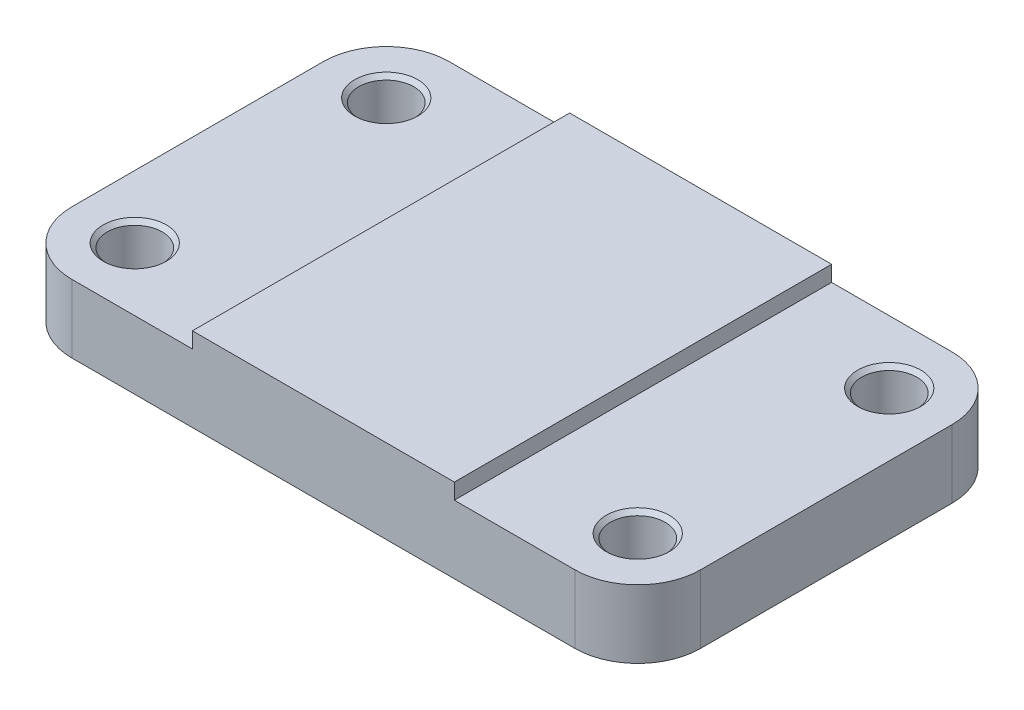
SolidWorks part; units mm, degrees
material "Ductile Iron"
ref_plane "Front Plane" through (0, 0, 0) normal (0, 0, 1) x (1, 0, 0)
ref_plane "Top Plane" through (0, 0, 0) normal (0, 1, 0) x (1, 0, 0)
ref_plane "Right Plane" through (0, 0, 0) normal (1, 0, 0) x (0, 0, -1)
sketch "Sketch1" plane through (0, 0, 0) normal (0, 0, 1) x (1, 0, 0)
  line L0 (0, -50.4344) -> (0, 50.4344) construction
  line L1 (-60, -6.5) -> (60, -6.5)
  line L2 (-60, -6.5) -> (-60, 6.5)
  line L3 (-60, 6.5) -> (60, 6.5)
  line L4 (60, -6.5) -> (60, 6.5)
  line L5 (-60, -6.5) -> (60, 6.5) construction
  line L6 (-60, 6.5) -> (60, -6.5) construction
  line L7 (-25, 6.5) -> (25, 6.5)
  line L8 (-25, 6.5) -> (-25, 9.5)
  line L9 (-25, 9.5) -> (25, 9.5)
  line L10 (25, 6.5) -> (25, 9.5)
  line L11 (-28, -6.5) -> (-25.5634, -4.0634)
  line L12 (-25.5634, -4.0634) -> (25.5634, -4.0634)
  line L13 (28, -6.5) -> (25.5634, -4.0634)
  point P0 (0, 0)
  point P10 (25, 8)
  point P13 (0, 0)
  point P19 (0, -4.0634)
  dimension "D1" = 13
  dimension "D2" = 120
  dimension "D3" = 3
  dimension "D4" = 25
  dimension "D5" = 25
  dimension "D6" = 2.4366
  dimension "D7" = 45
  dimension "D8" = 28
extrude "Boss-Extrude1" add sketch "Sketch1" along normal blind 36 and the other way blind 36 contours L3 L10 L9 L8 | L1 L4 L3 L2 region at (0, 8, 0)
fillet "Fillet1" radius 12 4 edges at (-60, 0, -36) (-60, 0, 36) (60, 0, -36) (60, 0, 36)
hole_wizard "M12x1.5 Tapped Hole1" positions "Sketch4" profile "Sketch5" tap size "M12x1.5" standard "ISO" end condition through all
sketch "Sketch4" plane through (0, 6.5, 0) normal (0, 1, 0) x (1, 0, 0)
  point P0 (-48, -24)
  point P3 (-48, 24)
  point P6 (48, 24)
  point P9 (48, -24)
sketch "Sketch5" plane through (-48, 6.5, 24) normal (1, 0, 0) x (0, 0, 1)
  line L0 (0, 0) -> (0, 13)
  line L1 (0, 13) -> (5.25, 13)
  line L2 (5.25, 13) -> (5.25, 0.775)
  line L3 (5.25, 0.775) -> (6.025, 0)
  line L5 (6.025, 0) -> (0, 0)
  line L6 (-5.25, 0.775) -> (-6.025, 0) construction
  line L11 (0, -6.35) -> (0, 107.95) construction
  dimension "Thru Tap Drill Dia." = 10.5
  dimension "Thru Tap Drill Depth" = 13
  dimension "Near C'Sink Dia." = 12.05
  dimension "Near C'Sink Angle" = 90
cosmetic thread "Hole Thread1" parameters "D2"=12
cosmetic thread "Hole Thread2" parameters "D2"=12
cosmetic thread "Hole Thread3" parameters "D2"=12
cosmetic thread "Hole Thread4" parameters "D2"=12
